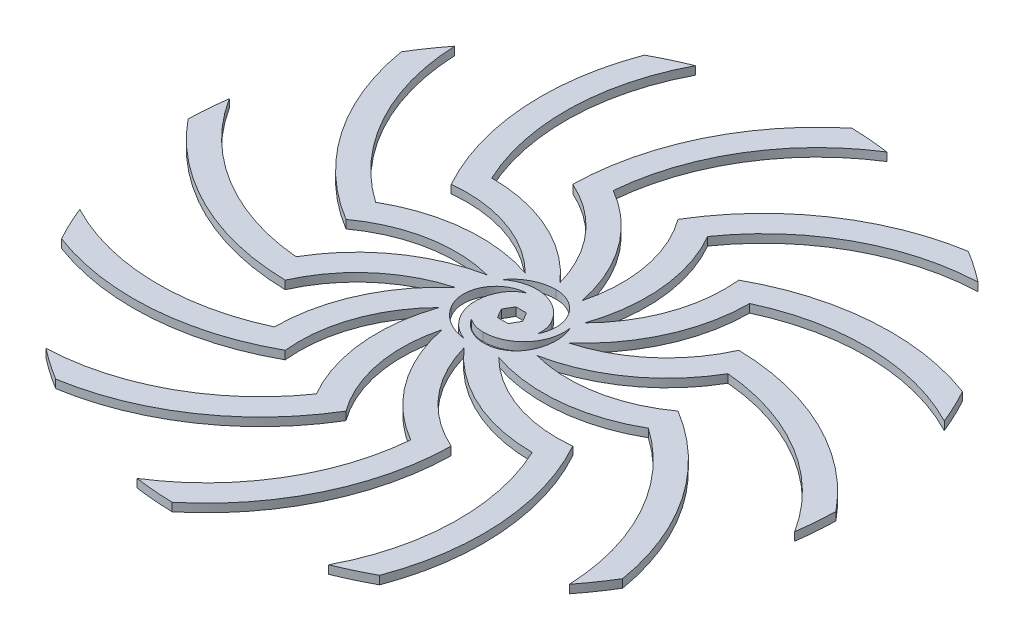
SolidWorks part; units mm, degrees
ref_plane "Front Plane" through (0, 0, 0) normal (0, 0, 1) x (1, 0, 0)
ref_plane "Top Plane" through (0, 0, 0) normal (0, 1, 0) x (1, 0, 0)
ref_plane "Right Plane" through (0, 0, 0) normal (1, 0, 0) x (0, 0, -1)
sketch "Sketch1" plane through (0, 0, 0) normal (0, 1, 0) x (1, 0, 0)
  line L0 (0, 0) -> (3.5728, 0)
  line L1 (0, 0) -> (0, 40) construction
  circle A0 centre (0, 0) radius 40
  circle A1 centre (0, 0) radius 42
  arc A2 (0, 0) -> (0, 20) centre (-13.7477, 10) ccw
  arc A3 (3.5728, 0) -> (3.5728, 20) centre (-13.7477, 10) ccw
  arc A4 (0, 20) -> (20.8254, 34.1512) centre (25.7173, 4.5527) cw
  arc A5 (3.5728, 20) -> (24.614, 31.5301) centre (25.7173, 4.5527) cw
  point P13 (0, 20)
  dimension "D1" = 80
  dimension "D2" = 84
  dimension "D3" = 17
  dimension "D4" = 20
  dimension "D5" = 30
  dimension "D6" = 27
extrude "Boss-Extrude1" add sketch "Sketch1" along normal blind 1 contours A3 A5 A0 A4 A2 L0 region at (3.6732, 0, -10)
ref_axis "Axis1" through (0, 0, 0) along (0, 1, 0)
pattern_circular "CirPattern1" count 12 over 360 about axis through (0, 0, 0) along (0, 1, 0) of bodies 101
sketch "Sketch2" plane through (0, 0, 0) normal (0, 1, 0) x (1, 0, 0)
  arc A0 (0, 0) -> (20, 0) centre (10, 13.7477) ccw construction
  arc A1 (1.7864, -3.0941) -> (19.1069, 6.9059) centre (1.7864, 16.9059) ccw construction
  arc A2 (0, 0) -> (20, 0) centre (10, 13.7477) ccw
  arc A3 (1.7864, -3.0941) -> (19.1069, 6.9059) centre (1.7864, 16.9059) ccw
  circle A4 centre (0, 0) radius 6.3246
  point P7 (5.7174, -2.704)
extrude "Boss-Extrude2" add sketch "Sketch2" along normal up to surface (1 mm away) contours A4 region at (5.9964, 0, 1.3465) up to face at (-20.5854, 1, 1.1757)
sketch "Sketch3" plane through (0, 1, 0) normal (0, 1, 0) x (1, 0, 0)
  line L0 (0, 0) -> (0, 1.4123) construction
  arc A0 (-2.1651, 1.25) -> (4.6112, -2.6623) centre (1.2231, -0.7061) ccw
  circle A1 centre (0, 0) radius 6.3246
  circle A2 centre (0, 0) radius 6.3246
  arc A3 (-3.0311, 1.75) -> (-0.5188, -5.2992) centre (1.2231, -0.7061) ccw
  circle A4 centre (0, 0) radius 5.3246
  circle A5 centre (0, 0) radius 2.5
  arc A6 (0, -2.5) -> (0, 5.3246) centre (0, 1.4123) ccw
  circle A7 centre (0, 0) radius 3.5
  arc A8 (0, -3.5) -> (4.8487, 2.2003) centre (0, 1.4123) ccw
  arc A9 (2.1651, 1.25) -> (-4.6112, -2.6623) centre (-1.2231, -0.7061) ccw
  arc A10 (3.0311, 1.75) -> (-4.3299, 3.0989) centre (-1.2231, -0.7061) ccw
  dimension "D3" = 5
  dimension "D4" = 7
  dimension "D1" = 0
  dimension "D2" = 1
  dimension "D5" = 3
extrude "Cut-Extrude1" cut sketch "Sketch3" against normal through all contours A7 A9 A4 A3 | A10 A7 A6 A4 | A8 A7 A0 A4 region at (2.7046, 1, 2.7563) region at (-3.7394, 1, 0.9641) region at (1.0347, 1, -3.7204)
scale "Scale1" scale about centroid uniform scaling yes scale factor 3.4
sketch "Sketch4" plane through (0, 2.2, 0) normal (0, 1, 0) x (1, 0, 0)
  line L1 (0, 7.3323) -> (-6.35, 3.6662) construction
  line L2 (-6.35, 3.6662) -> (-6.35, -3.6662) construction
  line L3 (-6.35, -3.6662) -> (0, -7.3323) construction
  line L4 (0, -7.3323) -> (6.35, -3.6662) construction
  line L5 (6.35, -3.6662) -> (6.35, 3.6662) construction
  line L6 (6.35, 3.6662) -> (0, 7.3323) construction
  line L7 (2.175, -3.7672) -> (4.35, 0)
  line L8 (4.35, 0) -> (2.175, 3.7672)
  line L9 (2.175, 3.7672) -> (-2.175, 3.7672)
  line L10 (-2.175, 3.7672) -> (-4.35, 0)
  line L11 (-4.35, 0) -> (-2.175, -3.7672)
  line L12 (-2.175, -3.7672) -> (2.175, -3.7672)
  circle A0 centre (0, 0) radius 6.35 construction
  circle A1 centre (0, 0) radius 4.35
  circle A2 centre (0, 0) radius 3.7672 construction
  dimension "D1" = 12.7
  dimension "D2" = 2
extrude "Cut-Extrude2" cut sketch "Sketch4" against normal up to surface (3.4 mm away) contours L11 L12 L7 L8 L9 L10 region at (0, 2.2, 0) up to face at (7.8986, -1.2, 8.4784)
